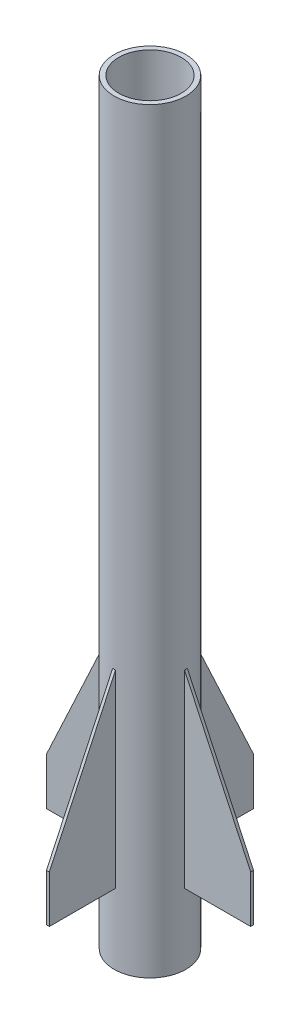
SolidWorks part; units mm, degrees
ref_plane "Front Plane" through (0, 0, 0) normal (0, 0, 1) x (1, 0, 0)
ref_plane "Top Plane" through (0, 0, 0) normal (0, 1, 0) x (1, 0, 0)
ref_plane "Right Plane" through (0, 0, 0) normal (1, 0, 0) x (0, 0, -1)
sketch "Sketch1" plane through (0, 0, 0) normal (0, 0, 1) x (1, 0, 0)
  line L0 (76, 0) -> (76, 1600)
  line L1 (0, 0) -> (0, 2000) construction
  line L9 (66, 0) -> (66, 1600)
  line L10 (76, 0) -> (66, 0)
  line L11 (76, 1600) -> (66, 1600)
  point P7 (65, 1600)
  point P8 (-1029.1667, 1600)
  point P9 (-9.3208, 1996.3774)
  dimension "D1" = 1600
  dimension "D2" = 76
  dimension "D3" = 2000
  dimension "D4" = 10
revolve "Revolve1" add sketch "Sketch1" angle 360 about L1
sketch "Sketch2" plane through (0, 0, 0) normal (0, 0, 1) x (1, 0, 0)
  line L5 (-76, 550) -> (-76, 150)
  line L6 (-76, 1600) -> (-76, 0) construction
  line L7 (-76, 150) -> (-216, 150)
  line L8 (-216, 150) -> (-216, 250)
  line L9 (-216, 250) -> (-76, 550)
  dimension "D1" = 400
  dimension "D2" = 140
  dimension "D3" = 100
  dimension "D4" = 150
extrude "Boss-Extrude1" add sketch "Sketch2" along normal blind 3 and the other way blind 3 separate body contours L9 L5 L7 L8
sketch "Sketch4" plane through (-76, 0, 0) normal (1, 0, 0) x (0, 0, -1)
  line L0 (3, 150) -> (-3, 150) construction
  line L1 (3, 550) -> (3, 150) construction
  line L2 (3, 550) -> (-3, 550) construction
  line L3 (-3, 550) -> (-3, 150) construction
  line L4 (3, 150) -> (-3, 150)
  line L5 (3, 550) -> (3, 150)
  line L6 (3, 550) -> (-3, 550)
  line L7 (-3, 550) -> (-3, 150)
sketch "Sketch5" plane through (0, 0, 0) normal (0, 0, 1) x (1, 0, 0)
  line L0 (0, 0) -> (0, 930.568) construction
pattern_circular "CirPattern2" count 4 over 360 about axis through (0, 0, 0) along (0, 1, 0) of bodies 102
